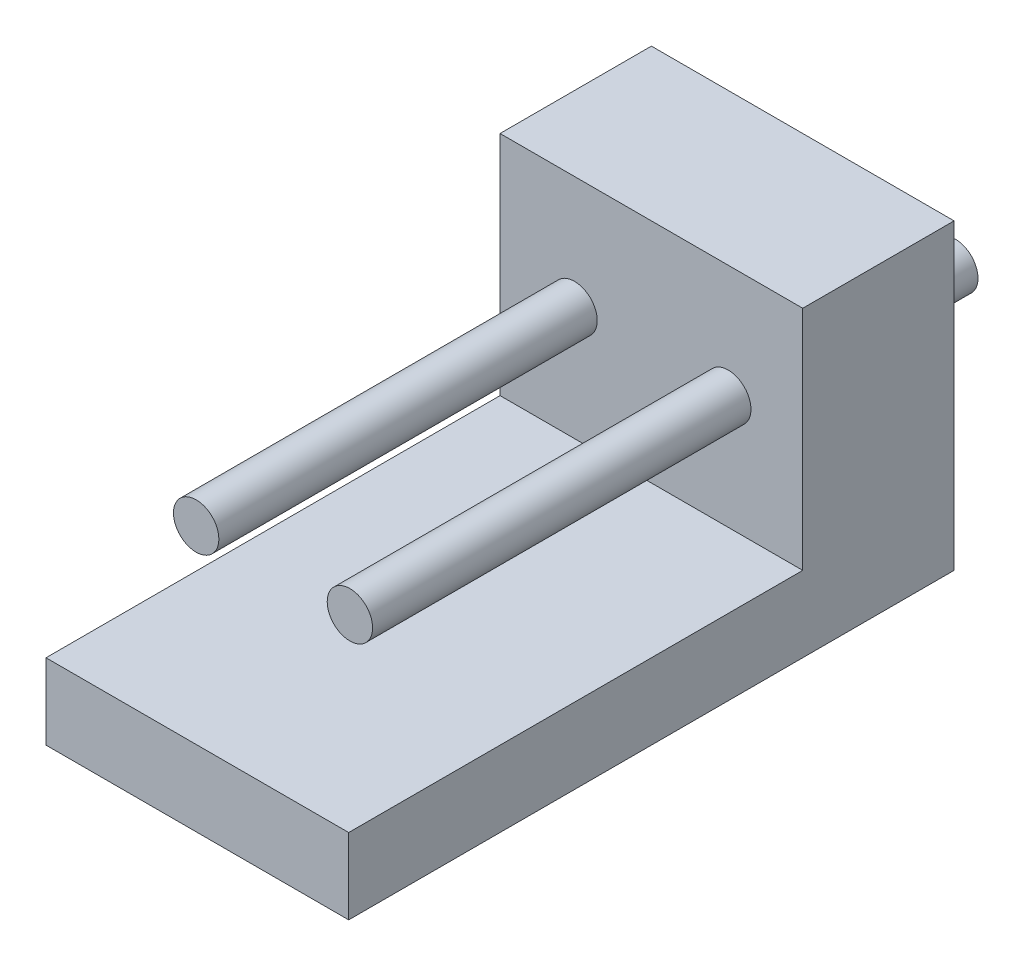
SolidWorks part; units mm, degrees
ref_plane "Спереди" through (0, 0, 0) normal (0, 0, 1) x (1, 0, 0)
ref_plane "Сверху" through (0, 0, 0) normal (0, 1, 0) x (1, 0, 0)
ref_plane "Справа" through (0, 0, 0) normal (1, 0, 0) x (0, 0, -1)
sketch "Эскиз1" plane through (0, 0, 0) normal (0, 0, 1) x (1, 0, 0)
  line L1 (0, 0) -> (10, 0)
  line L2 (0, 0) -> (0, 10)
  line L3 (0, 10) -> (10, 10)
  line L4 (10, 0) -> (10, 10)
  dimension "D1" = 10
  dimension "D2" = 10
extrude "Вытянуть1" add sketch "Эскиз1" along normal blind 5
sketch "Эскиз2" plane through (0, 0, 5) normal (0, 0, 1) x (1, 0, 0)
  line L1 (10, 0) -> (10, 10) construction
  line L2 (0, 0) -> (10, 0)
  line L3 (0, 0) -> (0, 2.5)
  line L4 (0, 2.5) -> (10, 2.5)
  line L7 (10, 0) -> (10, 2.5)
  dimension "D1" = 2.5
extrude "Вытянуть2" add sketch "Эскиз2" along normal blind 15
sketch "Эскиз3" plane through (0, 0, 5) normal (0, 0, 1) x (1, 0, 0)
  line L3 (5, 12.0229) -> (5, -0.8356) construction
  line L4 (0, 10) -> (0, 2.5) construction
  line L5 (10, 2.5) -> (10, 10) construction
  line L7 (5, 6.25) -> (10.08, 6.25) construction
  line L9 (10, 10) -> (0, 10) construction
  circle A0 centre (7.54, 6.25) radius 0.75
  circle A3 centre (2.46, 6.25) radius 0.75
  dimension "D3" = 3.75
  dimension "D4" = 5.08
extrude "Вытянуть3" add sketch "Эскиз3" along normal blind 12.5 and the other way blind 7.5
